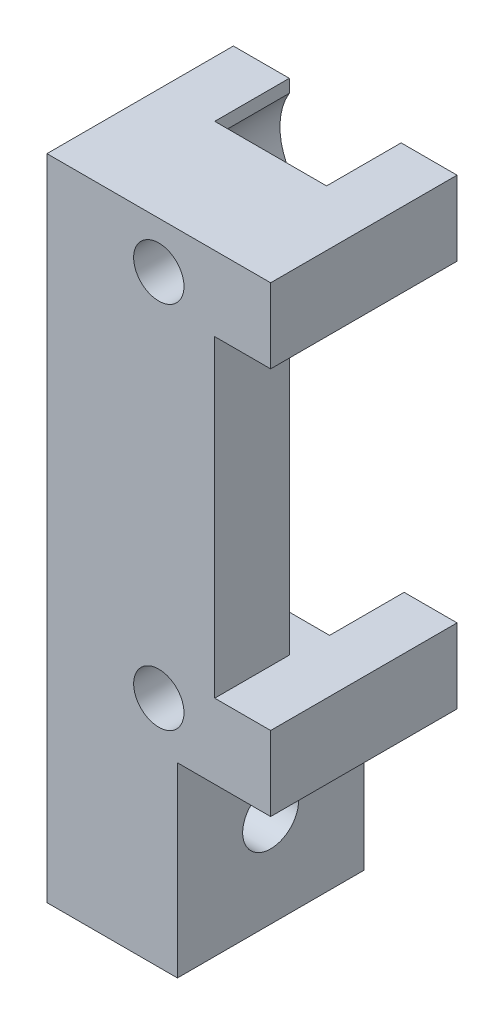
SolidWorks part; units mm, degrees
ref_plane "Front Plane" through (0, 0, 0) normal (0, 0, 1) x (1, 0, 0)
ref_plane "Top Plane" through (0, 0, 0) normal (0, 1, 0) x (1, 0, 0)
ref_plane "Right Plane" through (0, 0, 0) normal (1, 0, 0) x (0, 0, -1)
ref_axis "Axis2" through (0, 11, 0) along (0, -1, 0)
ref_plane "Plane2" through (0, 0, -150) normal (0, 0, 1) x (1, 0, 0)
sketch "Sketch7" plane through (0, 0, -150) normal (0, 0, 1) x (1, 0, 0)
  line L1 (-6, 24.8) -> (6, 24.8)
  line L2 (-6, 24.8) -> (-6, 0)
  line L4 (6, 24.8) -> (6, 0)
  line L7 (-6, 0) -> (6, 0)
  point P6 (6, 0)
  point P8 (0, 0)
  point P11 (0, 24.8)
  dimension "D1" = 24.8
  dimension "D2" = 12
extrude "Main" add sketch "Sketch7" along normal mid plane 10
sketch "Sketch8" plane through (0, 0, -145) normal (0, 0, 1) x (1, 0, 0)
  line L1 (-6, 24.8) -> (-6, 0) construction
  line L2 (6, 24.8) -> (-6, 24.8) construction
  circle A0 centre (0, 22.3) radius 1.35
  circle A1 centre (0, 2.5) radius 1.35
  dimension "D1" = 2.7
  dimension "D2" = 2.5
  dimension "D3" = 19.8
  dimension "D4" = 6
extrude "Holes" cut sketch "Sketch8" against normal through all
sketch "Sketch16" plane through (6, 0, 0) normal (1, 0, 0) x (0, 0, -1)
  line L1 (149, 20.8) -> (155, 20.8)
  line L2 (149, 20.8) -> (149, 4)
  line L3 (149, 4) -> (155, 4)
  line L4 (155, 20.8) -> (155, 4)
  line L5 (155, 0) -> (155, 24.8) construction
  dimension "D1" = 6
  dimension "D2" = 4
  dimension "D3" = 4
extrude "FixExtrusion" cut sketch "Sketch16" against normal through all
sketch "Sketch17" plane through (0, 0, -155) normal (0, 0, -1) x (-1, 0, 0)
  line L0 (-6, 24.8) -> (6, 24.8) construction
  line L1 (-3, 24.8) -> (3, 24.8)
  line L2 (-3, 24.8) -> (-3, 0)
  line L3 (-3, 0) -> (3, 0)
  line L4 (3, 24.8) -> (3, 0)
  line L5 (6, 0) -> (-6, 0) construction
  line L6 (-6, 20.8) -> (-6, 24.8) construction
  dimension "D1" = 6
  dimension "D2" = 3
extrude "Cut-Extrude1" cut sketch "Sketch17" against normal blind 4
sketch "Sketch18" plane through (0, 0, -149) normal (0, 0, -1) x (-1, 0, 0)
  line L0 (6, 4) -> (-6, 4) construction
  line L1 (-6, 20.8) -> (-3, 20.8)
  line L2 (-6, 20.8) -> (-6, 4)
  line L3 (-6, 4) -> (-3, 4)
  line L4 (-3, 20.8) -> (-3, 4)
  dimension "D1" = 3
extrude "Cut-Extrude2" cut sketch "Sketch18" against normal through all
sketch "Sketch19" plane through (0, 0, 0) normal (0, -1, 0) x (1, 0, 0)
  line L0 (1, -155) -> (-6, -155)
  line L1 (-6, -155) -> (-6, -151.45)
  line L2 (-6, -151.45) -> (-7, -151.45)
  line L3 (-7, -151.45) -> (-7, -148.55)
  line L4 (-7, -148.55) -> (-6, -148.55)
  line L5 (-6, -148.55) -> (-6, -145)
  line L6 (-6, -145) -> (1, -145)
  line L7 (1, -145) -> (1, -155)
  line L8 (6, -145) -> (-6, -145) construction
  line L9 (-6, -145) -> (-6, -155) construction
  dimension "D1" = 10
  dimension "D2" = 1
  dimension "D3" = 2.9
  dimension "D4" = 7
extrude "Boss-Extrude1" add sketch "Sketch19" along normal blind 10
sketch "Sketch20" plane through (1, 0, 0) normal (1, 0, 0) x (0, 0, -1)
  line L0 (155, -10) -> (145, -10) construction
  line L1 (155, -10) -> (155, 0) construction
  circle A0 centre (150, -5) radius 1.5
  point P4 (150, -10)
  dimension "D1" = 3
  dimension "D2" = 5
  dimension "D3" = 5
extrude "Cut-Extrude3" cut sketch "Sketch20" against normal through all
sketch "Sketch21" plane through (0, 0, -155) normal (0, 0, -1) x (-1, 0, 0)
  circle A0 centre (0, 2.5) radius 3.5
  circle A1 centre (0, 2.5) radius 1.35 construction
  circle A2 centre (0, 22.3) radius 3.5
  circle A3 centre (0, 22.3) radius 1.35 construction
  dimension "D1" = 7
extrude "Cut-Extrude4" cut sketch "Sketch21" against normal up to surface (4 mm away) up to face at (0.2, 1.6, -151)
